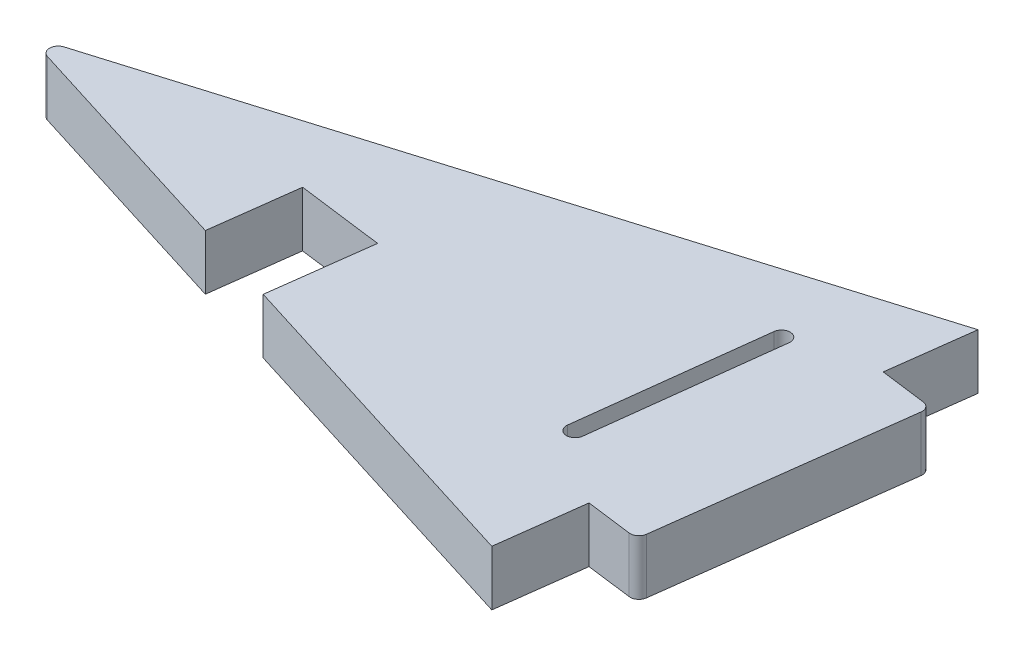
SolidWorks part; units mm, degrees
material "Balsa"
ref_plane "Front Plane" through (0, 0, 0) normal (0, 0, 1) x (1, 0, 0)
ref_plane "Top Plane" through (0, 0, 0) normal (0, 1, 0) x (1, 0, 0)
ref_plane "Right Plane" through (0, 0, 0) normal (1, 0, 0) x (0, 0, -1)
sketch "Sketch1" plane through (0, 0, 0) normal (0, 1, 0) x (1, 0, 0)
  line L0 (-2.5866, -0.183) -> (-1.3066, 9.7348)
  line L1 (3.8134, 49.4057) -> (-80.123, 24.0471)
  line L2 (-80.123, 24.0471) -> (-50.5622, 14.8094)
  line L3 (2.5652, 39.7347) -> (8.8628, 38.922)
  line L4 (8.8628, 38.922) -> (4.9911, 8.922)
  line L5 (4.9911, 8.922) -> (-1.3066, 9.7348)
  line L6 (2.5652, 39.7347) -> (3.8134, 49.4057)
  line L7 (-50.5622, 14.8094) -> (-49.2822, 24.7271)
  line L8 (-49.2822, 24.7271) -> (-39.3645, 23.4471)
  line L9 (-39.3645, 23.4471) -> (-40.8702, 11.7806)
  line L10 (-40.8702, 11.7806) -> (-2.5866, -0.183)
  line L11 (-6.7585, 37.3511) -> (-9.3198, 16.1487) construction
  line L12 (-5.7657, 37.2312) -> (-8.327, 16.0287)
  line L13 (-7.7512, 37.471) -> (-10.3126, 16.2686)
  arc A0 (-5.7657, 37.2312) -> (-7.7512, 37.471) centre (-6.7585, 37.3511) ccw
  arc A1 (-10.3126, 16.2686) -> (-8.327, 16.0287) centre (-9.3198, 16.1487) ccw
  point P11 (-1.9466, 4.7759)
  point P12 (-8.0391, 26.7499)
  dimension "D1" = 50
  dimension "D2" = 80
  dimension "D3" = 80
  dimension "D4" = 6.3498
  dimension "D5" = 30
  dimension "D6" = 6.35
  dimension "D7" = 10
  dimension "D8" = 10
  dimension "D9" = 10
  dimension "D10" = 39.5
  dimension "D11" = 1
extrude "Boss-Extrude1" add sketch "Sketch1" along normal blind 6.35
fillet "Fillet1" radius 1 3 edges at (4.9911, 3.175, -8.922) (8.8628, 3.175, -38.922) (-80.123, 3.175, -24.0471)
